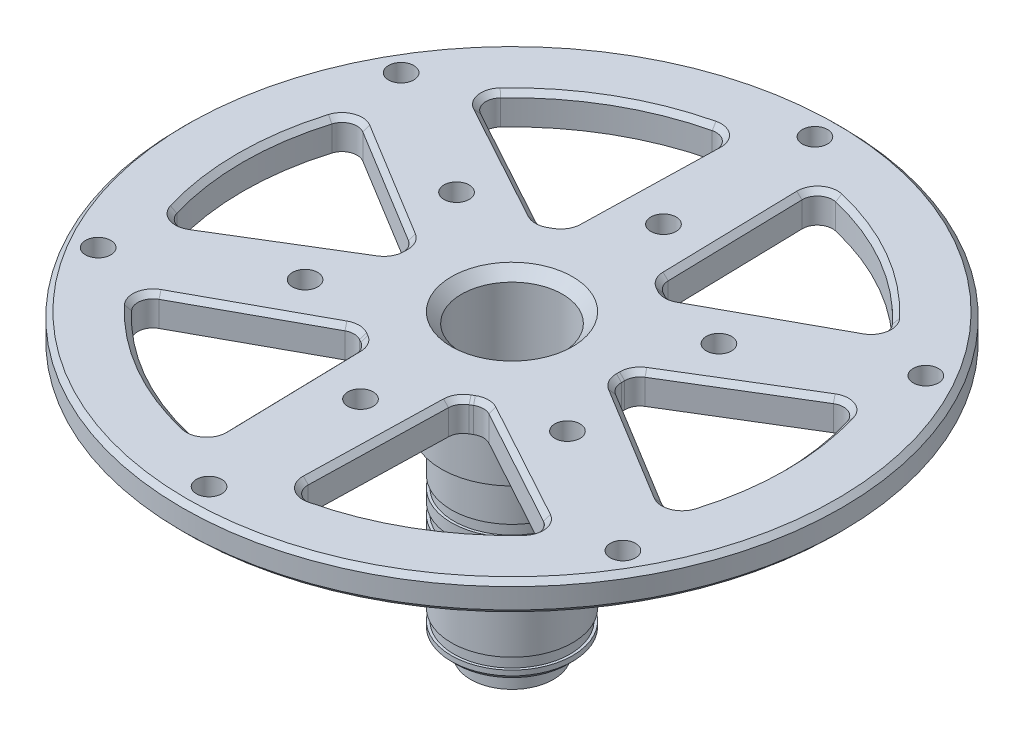
SolidWorks part; units mm, degrees
ref_plane "Front Plane" through (0, 0, 0) normal (0, 0, 1) x (1, 0, 0)
ref_plane "Top Plane" through (0, 0, 0) normal (0, 1, 0) x (1, 0, 0)
ref_plane "Right Plane" through (0, 0, 0) normal (1, 0, 0) x (0, 0, -1)
ref_axis "Axis1" through (0, 0, 0) along (0, 1, 0)
sketch "Sketch2" plane through (0, 0, 0) normal (0, 0, 1) x (1, 0, 0)
  line L0 (0, 0) -> (0, -45684.8392) construction
  line L1 (-4, 10) -> (-4, -6.5)
  line L2 (-4, -6.5) -> (-3.1, -6.5)
  line L3 (-3.1, -6.5) -> (-3.1, -9.5)
  line L4 (-3.1, -9.5) -> (-4.1, -9.5)
  line L5 (-4.1, -9.5) -> (-4.1, -7.5)
  line L6 (-4.1, -7.5) -> (-6, -7.5)
  line L7 (-6, -7.5) -> (-6, 10)
  line L9 (-11.5, -12.5) -> (11.5, -12.5) construction
  line L18 (-7, 17) -> (-7, 10)
  line L20 (-4, 10) -> (-5, 11)
  line L21 (-5, 20) -> (-32.65, 20)
  line L25 (-32.65, 17) -> (-7, 17)
  line L27 (31.65, 16) -> (-31.65, 16) construction
  line L28 (-20.098, 13.65) -> (-20.098, 18.273) construction
  line L31 (-5, 11) -> (-5, 20)
  line L37 (-7, 10) -> (-6, 10)
  line L40 (8.8, 10) -> (-8.8, 10) construction
  line L43 (-32.65, 17) -> (-32.65, 20)
  line L44 (-32.65, 15) -> (-32.65, 4) construction
  dimension "D1" = 8
  dimension "D3" = 8.2
  dimension "D4" = 12
  dimension "D5" = 2
  dimension "D6" = 1
  dimension "D7" = 1
  dimension "D8" = 2
  dimension "D9" = 5
  dimension "D10" = 1
  dimension "D12" = 3
  dimension "D13" = 1
  dimension "D15" = 20.098
  dimension "D20" = 10
  dimension "D21" = 135
revolve "Revolve1" add sketch "Sketch2" angle 360 about L0
sketch "Sketch3" plane through (0, 0, 0) normal (0, 0, 1) x (1, 0, 0)
  line L0 (-20.098, 18.273) -> (-20.098, -49187.0734) construction
  line L1 (-21.598, 15) -> (-22.598, 15)
  line L2 (-22.598, 15) -> (-22.598, 17)
  line L4 (-20.098, 17) -> (-20.098, 11)
  line L5 (-20.098, 11) -> (-21.598, 11)
  line L6 (-21.598, 15) -> (-21.598, 11)
  line L7 (-32.65, 17) -> (32.65, 17) construction
  line L8 (-22.598, 17) -> (-20.098, 17)
  line L9 (-18.398, 15) -> (-21.798, 15) construction
  dimension "D1" = 3
  dimension "D2" = 4
  dimension "D3" = 1
revolve "Revolve2" add sketch "Sketch3" angle 360 about L0
pattern_circular "CirPattern1" count 3 over 360 about axis through (0, 0, 0) along (0, 1, 0) of "Revolve2"
chamfer "Chamfer1" distance 0.5 angle 45 2 edges at (0, 20, 32.65) (0, 17, 32.65)
chamfer "Chamfer2" distance 1 angle 45 1 edges at (0, 20, 5)
sketch "Sketch6" plane through (0, 0, 0) normal (0, 1, 0) x (1, 0, 0)
  line L0 (0, 0) -> (50000, 0) construction
  line L1 (24.8992, -9.5) -> (10.9545, -1)
  line L2 (10.9545, 1) -> (24.8992, 9.5)
  arc A0 (24.8992, -9.5) -> (24.8992, 9.5) centre (0, 0) ccw
  arc A1 (10.9545, -1) -> (10.9545, 1) centre (0, 0) ccw
  circle A3 centre (0, 0) radius 32.65 construction
  circle A4 centre (0, 0) radius 7 construction
  dimension "D1" = 4
  dimension "D2" = 6
  dimension "D3" = 2
  dimension "D4" = 19
extrude "Cut-Extrude1" cut sketch "Sketch6" along normal through all
fillet "Fillet1" radius 1.5 4 edges at (24.8992, 18.5, 9.5) (10.9545, 18.5, 1) (10.9545, 18.5, -1) (24.8992, 18.5, -9.5)
hole_wizard "M3x0.5 Tapped Hole1" positions "Sketch7" profile "Sketch8" tap size "M3x0.5" standard "ANSI Metric" end condition through all
sketch "Sketch7" plane through (0, 20, 0) normal (0, 1, 0) x (1, 0, 0)
  line L0 (0, 0) -> (12.9904, -7.5) construction
  line L3 (0, 0) -> (0, -9.9462) construction
  circle A0 centre (0, 0) radius 15 construction
  circle A1 centre (0, 0) radius 30 construction
  point P2 (12.9904, -7.5)
  dimension "D1" = 60
  dimension "D2" = 30
  dimension "D3" = 60
sketch "Sketch8" plane through (12.9904, 20, 7.5) normal (1, 0, 0) x (0, 0, 1)
  line L0 (0, 0) -> (0, 29.5)
  line L1 (0, 29.5) -> (1.25, 29.5)
  line L2 (1.25, 29.5) -> (1.25, 0)
  line L5 (1.25, 0) -> (0, 0)
  line L11 (0, -6.35) -> (0, 107.95) construction
  dimension "Thru Tap Drill Dia." = 2.5
  dimension "Thru Tap Drill Depth" = 29.5
cosmetic thread "Hole Thread3" parameters "D2"=3
pattern_circular "CirPattern2" count 6 over 360 about axis through (0, 0, 0) along (0, 1, 0) of "Cut-Extrude1", "Fillet1", "M3x0.5 Tapped Hole1"
sketch "Sketch9" plane through (0, 0, 0) normal (0, 0, 1) x (1, 0, 0)
  line L0 (0, 0) -> (0, -50000) construction
  line L1 (-8.5387, -5.4) -> (-5.75, -5.4)
  line L3 (-6.5, -6.5) -> (-5.75, -6.5)
  line L4 (-5.75, -5.4) -> (-5.75, -6.5)
  line L6 (-6.5, -6.5) -> (-5.5, -7.5)
  line L7 (-5.5, -7.5) -> (-8.5387, -7.5)
  line L8 (-8.5387, -7.5) -> (-8.5387, -5.4)
  line L9 (-6, -7.5) -> (6, -7.5) construction
  line L10 (-6, 10) -> (-6, -7.5) construction
  dimension "D1" = 11.5
  dimension "D2" = 1.1
  dimension "D3" = 45
  dimension "D4" = 1
  dimension "D5" = 0.5
revolve "Cut-Revolve1" cut sketch "Sketch9" angle 360 about L0
sketch "Sketch10" plane through (0, 0, 0) normal (0, 0, 1) x (1, 0, 0)
  line L0 (0, 0) -> (0, 50000) construction
  line L1 (-6.9577, 6) -> (-5.75, 6)
  line L2 (-6.9577, 6) -> (-6.9577, 4.9)
  line L3 (-6.9577, 4.9) -> (-5.75, 4.9)
  line L4 (-5.75, 6) -> (-5.75, 4.9)
  line L5 (-9, 6) -> (9, 6) construction
  dimension "D1" = 11.5
  dimension "D2" = 1.1
revolve "Cut-Revolve2" cut sketch "Sketch10" angle 360 about L0
sketch "Sketch11" plane through (0, 0, 0) normal (0, 0, 1) x (1, 0, 0)
  line L0 (0, 0) -> (0, -50000) construction
  line L1 (-8.902, 3.7) -> (-5.75, 3.7)
  line L2 (-8.902, 3.7) -> (-8.902, 2.6)
  line L3 (-8.902, 2.6) -> (-5.75, 2.6)
  line L4 (-5.75, 3.7) -> (-5.75, 2.6)
  line L7 (8.8, 2.6) -> (-8.8, 2.6) construction
  dimension "D1" = 11.5
  dimension "D2" = 1.1
revolve "Cut-Revolve3" cut sketch "Sketch11" angle 360 about L0
hole_wizard "M3x0.5 Tapped Hole2" positions "Sketch12" profile "Sketch13" tap size "M3x0.5" standard "ANSI Metric" end condition through all
sketch "Sketch12" plane through (0, 20, 0) normal (0, 1, 0) x (1, 0, 0)
  circle A0 centre (0, 0) radius 30 construction
  point P0 (0, 30)
  dimension "D1" = 60
sketch "Sketch13" plane through (0, 20, -30) normal (1, 0, 0) x (0, 0, 1)
  line L0 (0, 0) -> (0, 29.5)
  line L1 (0, 29.5) -> (1.25, 29.5)
  line L2 (1.25, 29.5) -> (1.25, 0)
  line L5 (1.25, 0) -> (0, 0)
  line L11 (0, -6.35) -> (0, 107.95) construction
  dimension "Thru Tap Drill Dia." = 2.5
  dimension "Thru Tap Drill Depth" = 29.5
cosmetic thread "Hole Thread4" parameters "D2"=3
pattern_circular "CirPattern3" count 6 over 360 about axis through (0, 0, 0) along (0, 1, 0) of "M3x0.5 Tapped Hole2"
chamfer "Chamfer3" distance 0.5 angle 45 48 edges at (-5.5, 20, -9.5263) (-4.8052, 20, -10.1415) (-6.3802, 20, -9.2321) (-4.4284, 20, -17.6625) (-13.082, 20, -12.6664) (-4.8214, 20, -25.6448) (-19.7984, 20, -16.9978) (-13.325, 20, -23.0796) (11, 20, 0) (11.1854, 20, 0.9094) (11.1854, 20, -0.9094) (17.5104, 20, 4.9961) (17.5104, 20, -4.9961) (24.6198, 20, 8.647) (24.6198, 20, -8.647) (26.65, 20, 0) (5.5, 20, -9.5263) (6.3802, 20, -9.2321) (4.8052, 20, -10.1415) (13.082, 20, -12.6664) (4.4284, 20, -17.6625) (19.7984, 20, -16.9978) (4.8214, 20, -25.6448) (13.325, 20, -23.0796) (-17.5104, 20, -4.9961) (-24.6198, 20, -8.647) (-11.1854, 20, -0.9094) (-26.65, 20, 0) (-11, 20, 0) (-24.6198, 20, 8.647) (-11.1854, 20, 0.9094) (-17.5104, 20, 4.9961) (-13.082, 20, 12.6664) (-19.7984, 20, 16.9978) (-6.3802, 20, 9.2321) (-13.325, 20, 23.0796) (-5.5, 20, 9.5263) (-4.8214, 20, 25.6448) (-4.8052, 20, 10.1415) (-4.4284, 20, 17.6625) (13.082, 20, 12.6664) (6.3802, 20, 9.2321) (19.7984, 20, 16.9978) (5.5, 20, 9.5263) (13.325, 20, 23.0796) (4.8052, 20, 10.1415) (4.8214, 20, 25.6448) (4.4284, 20, 17.6625)
